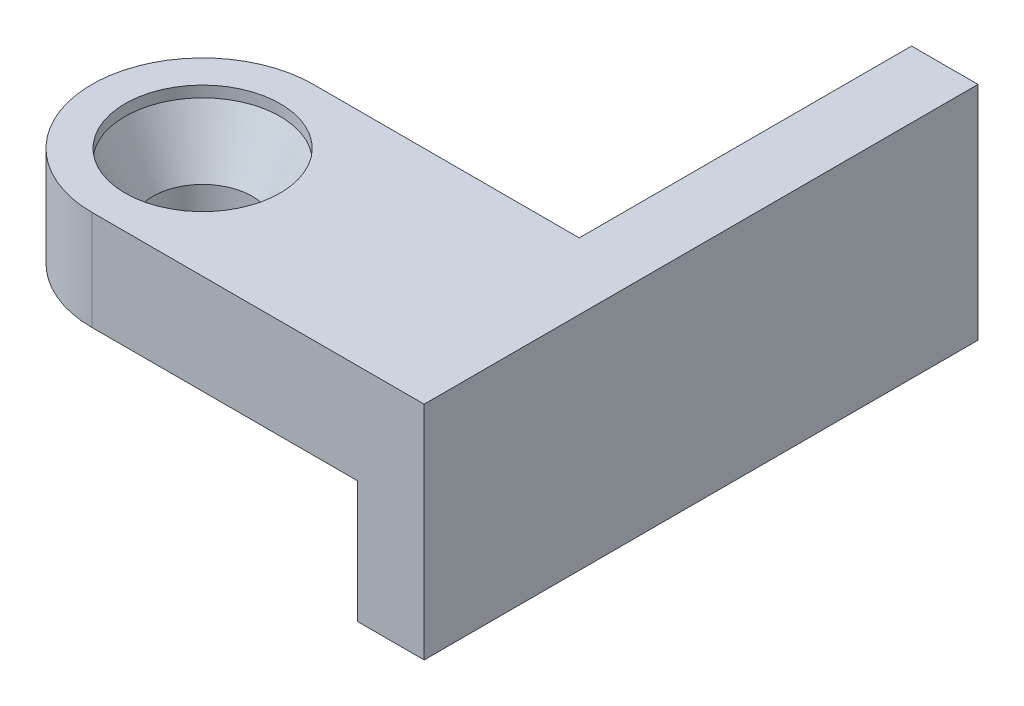
SolidWorks part; units mm, degrees
ref_plane "Front Plane" through (0, 0, 0) normal (0, 0, 1) x (1, 0, 0)
ref_plane "Top Plane" through (0, 0, 0) normal (0, 1, 0) x (1, 0, 0)
ref_plane "Right Plane" through (0, 0, 0) normal (1, 0, 0) x (0, 0, -1)
sketch "Sketch1" plane through (0, 0, 0) normal (0, 1, 0) x (1, 0, 0)
  line L0 (0, 5) -> (15, 5)
  line L1 (15, 5) -> (15, -5)
  line L2 (15, -5) -> (0, -5)
  circle A0 centre (0, 0) radius 2.25
  arc A1 (0, 5) -> (0, -5) centre (0, 0) ccw
  arc A2 (0, -5) -> (0, 5) centre (0, 0) ccw construction
  dimension "D1" = 4.5
  dimension "D2" = 10
  dimension "D3" = 15
extrude "Boss-Extrude1" add sketch "Sketch1" along normal blind 4.5
sketch "Sketch2" plane through (15, 0, 0) normal (1, 0, 0) x (0, 0, -1)
  line L1 (-5, 4.5) -> (20, 4.5)
  line L2 (-5, 4.5) -> (-5, -5.5)
  line L3 (-5, -5.5) -> (20, -5.5)
  line L4 (20, 4.5) -> (20, -5.5)
  dimension "D1" = 10
  dimension "D2" = 25
extrude "Boss-Extrude2" add sketch "Sketch2" against normal blind 3 contours L1 L4 L3 L2
sketch "Sketch3" plane through (0, 4.5, 0) normal (0, 1, 0) x (1, 0, 0)
  circle A0 centre (0, 0) radius 3.5
  dimension "D1" = 7
extrude "Cut-Extrude1" cut sketch "Sketch3" against normal blind 3
chamfer "Chamfer1" distance 2.5 distance2 1.25 1 edges at (0, 1.5, 3.5) first distance on face at (0, 1.5, 3.5)
